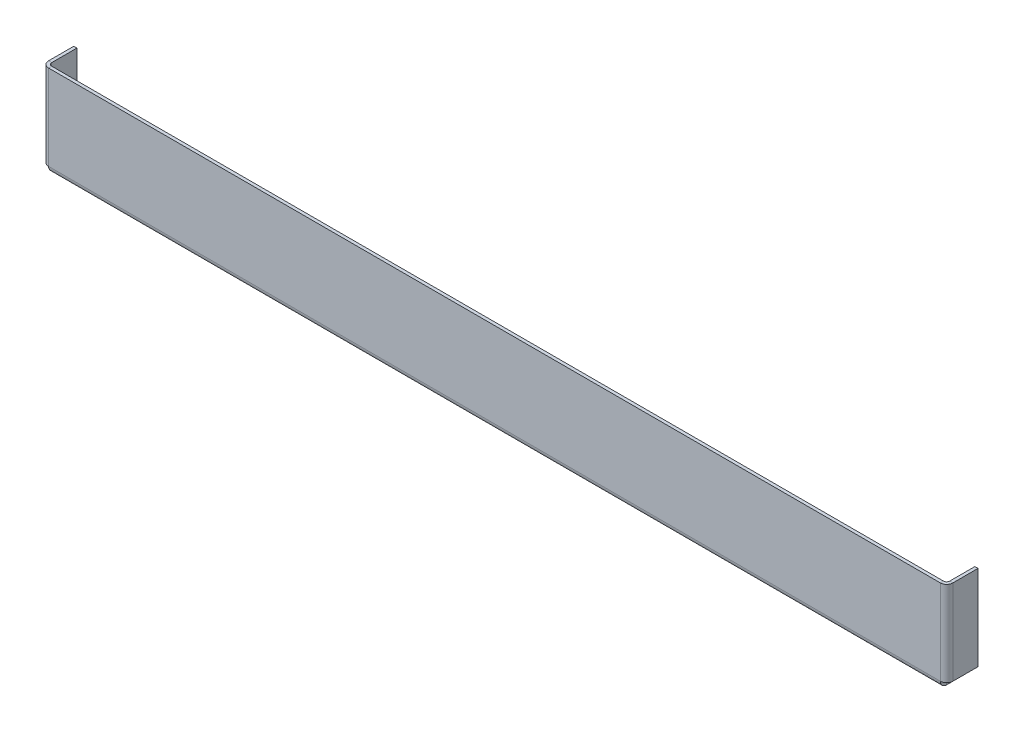
SolidWorks part; units mm, degrees
note: The reader was unsure of these and kept them because the rebuilt part matched: thickness of "Базовая кромка1", "Ребро-кромка2", "Ребро-кромка3", "Ребро-кромка4", "Листовой металл1", "Листовой металл3", "Листовой металл4", "Листовой металл5"; flange length of "Ребро-кромка2", "Ребро-кромка3", "Ребро-кромка4".
material "1060 Сплав"
ref_plane "Front" through (0, 0, 0) normal (0, 0, 1) x (1, 0, 0)
ref_plane "Top" through (0, 0, 0) normal (0, 1, 0) x (1, 0, 0)
ref_plane "Right" through (0, 0, 0) normal (1, 0, 0) x (0, 0, -1)
sketch "Эскиз1" plane through (0, 0, 0) normal (0, 0, 1) x (1, 0, 0)
  line L1 (0, 0) -> (426, 0)
  line L2 (0, 0) -> (0, 40.7)
  line L3 (0, 40.7) -> (426, 40.7)
  line L4 (426, 0) -> (426, 40.7)
  dimension "D1" = 40.7
  dimension "D2" = 426
base flange "Базовая кромка1" sketch "Эскиз1" thickness 1.5 reverse thickness direction no parameters "D1"=2
edge flange "Ребро-кромка2" sketch "Эскиз18" flange angle 90 flange length 15 flange position bend outside bend radius 1.5 thickness 1.5 relief rectangular parameters "D6"=10, "D8"=1
sketch "Эскиз18" plane through (0, 0, -1.5) normal (-1, 0, 0) x (0, 1, 0)
  line L0 (40.7, 0) -> (0, 0) construction
  line L1 (40.7, 0) -> (0, 0)
  line L2 (0, 0) -> (0, 13.5)
  line L3 (0, 13.5) -> (40.7, 13.5)
  line L4 (40.7, 13.5) -> (40.7, 0)
bend "EdgeBend4" bend radius 1.5 bend angle 90 parameters "D5"=4
edge flange "Ребро-кромка3" sketch "Эскиз21" flange angle 90 flange length 15 flange position bend outside bend radius 1.5 thickness 1.5 relief rectangular parameters "D6"=10
sketch "Эскиз21" plane through (0, 0, -1.5) normal (0, -1, 0) x (-1, 0, 0)
  line L2 (-426, 0) -> (-426, 13.5)
  line L3 (-426, 13.5) -> (0, 13.5)
  line L4 (0, 13.5) -> (0, 0)
  line L7 (0, 0) -> (-426, 0) construction
  line L8 (0, 0) -> (-426, 0)
bend "EdgeBend5" bend radius 1.5 bend angle 90 parameters "D5"=5
edge flange "Ребро-кромка4" sketch "Эскиз24" flange angle 90 flange length 15 flange position bend outside bend radius 1.5 thickness 1.5 relief rectangular parameters "D6"=10
sketch "Эскиз24" plane through (426, 0, -1.5) normal (1, 0, 0) x (0, -1, 0)
  line L0 (0, 0) -> (-40.7, 0) construction
  line L1 (0, 0) -> (-40.7, 0)
  line L2 (-40.7, 0) -> (-40.7, 13.5)
  line L3 (-40.7, 13.5) -> (0, 13.5)
  line L4 (0, 13.5) -> (0, 0)
bend "EdgeBend6" bend radius 1.5 bend angle 90 parameters "D5"=6
sketch "Сгиб-Линии1" [suppressed] plane through (0, 0, 0) normal (0, 1, 0) x (1, 0, 0)
sketch "Граничная рамка1" [suppressed] plane through (0, 0, 0) normal (0, 1, 0) x (1, 0, 0)
sheet metal parameters "Листовой металл1" thickness 1.5 parameters "D1"=2
flat pattern "Развертка1" [suppressed]
sketch "Сгиб-Линии2" plane through (0, 0, 0) normal (0, 1, 0) x (1, 0, 0)
sketch3d "Граничная рамка2" [suppressed]
  line L0 (0, 0, 0) -> (-432, 0, 0) construction
  line L1 (0, 43.7, 0) -> (-432, 43.7, 0) construction
  line L2 (0, 0, 0) -> (0, 43.7, 0) construction
  line L3 (-432, 0, 0) -> (-432, 43.7, 0) construction
sheet metal parameters "Листовой металл3" thickness 1.5 parameters "D1"=2, "D7"=2
flat pattern "Развертка1"
sketch "Сгиб-Линии2" plane through (0, 0, 0) normal (0, 0, 1) x (1, 0, 0)
  line L0 (432, 46.0562) -> (0, 46.0562) construction
  line L1 (432, 46.0562) -> (0, 46.0562) construction
  line L2 (-2.3562, 43.7) -> (-2.3562, 0) construction
  line L5 (-2.3562, 43.7) -> (-2.3562, 0) construction
sketch3d "Граничная рамка2" [suppressed]
  line L0 (-15.7124, 0, 0) -> (432, 0, 0) construction
  line L1 (-15.7124, 88.4124, 0) -> (432, 88.4124, 0) construction
  line L2 (-15.7124, 0, 0) -> (-15.7124, 88.4124, 0) construction
  line L3 (432, 0, 0) -> (432, 88.4124, 0) construction
bend of the flat pattern "Плоское состояние-<EdgeBend4>1"
sheet metal parameters "Листовой металл4" thickness 1.5 parameters "D1"=2, "D7"=2
flat pattern "Развертка1"
sketch "Сгиб-Линии2" plane through (0, 0, 0) normal (0, 0, 1) x (1, 0, 0)
  line L0 (432, 46.0562) -> (0, 46.0562) construction
  line L1 (432, 46.0562) -> (0, 46.0562) construction
  line L2 (-2.3562, 43.7) -> (-2.3562, 0) construction
  line L3 (0, -2.3562) -> (432, -2.3562) construction
  line L4 (0, -2.3562) -> (432, -2.3562) construction
  line L5 (-2.3562, 43.7) -> (-2.3562, 0) construction
sketch3d "Граничная рамка2" [suppressed]
  line L0 (-15.7124, -15.7124, 0) -> (432, -15.7124, 0) construction
  line L1 (-15.7124, 88.4124, 0) -> (432, 88.4124, 0) construction
  line L2 (-15.7124, -15.7124, 0) -> (-15.7124, 88.4124, 0) construction
  line L3 (432, -15.7124, 0) -> (432, 88.4124, 0) construction
bend of the flat pattern "Плоское состояние-<EdgeBend4>1"
bend of the flat pattern "Плоское состояние-<EdgeBend5>1"
sheet metal parameters "Листовой металл5" thickness 1.5 parameters "D1"=2, "D7"=2
flat pattern "Развертка1"
sketch "Сгиб-Линии2" plane through (0, 0, 0) normal (0, 0, 1) x (1, 0, 0)
  line L2 (-1.7671, 40.7) -> (-1.7671, 0) construction
  line L3 (0, -1.7671) -> (426, -1.7671) construction
  line L4 (0, -1.7671) -> (426, -1.7671) construction
  line L5 (-1.7671, 40.7) -> (-1.7671, 0) construction
  line L6 (427.7671, 0) -> (427.7671, 40.7) construction
  line L7 (427.7671, 0) -> (427.7671, 40.7) construction
sketch3d "Граничная рамка2" [suppressed]
  line L0 (-15.5343, -15.5343, 0) -> (441.5343, -15.5343, 0) construction
  line L1 (-15.5343, 40.7, 0) -> (441.5343, 40.7, 0) construction
  line L2 (-15.5343, -15.5343, 0) -> (-15.5343, 40.7, 0) construction
  line L3 (441.5343, -15.5343, 0) -> (441.5343, 40.7, 0) construction
bend of the flat pattern "Плоское состояние-<EdgeBend4>1"
bend of the flat pattern "Плоское состояние-<EdgeBend5>1"
bend of the flat pattern "Плоское состояние-<EdgeBend6>1"
